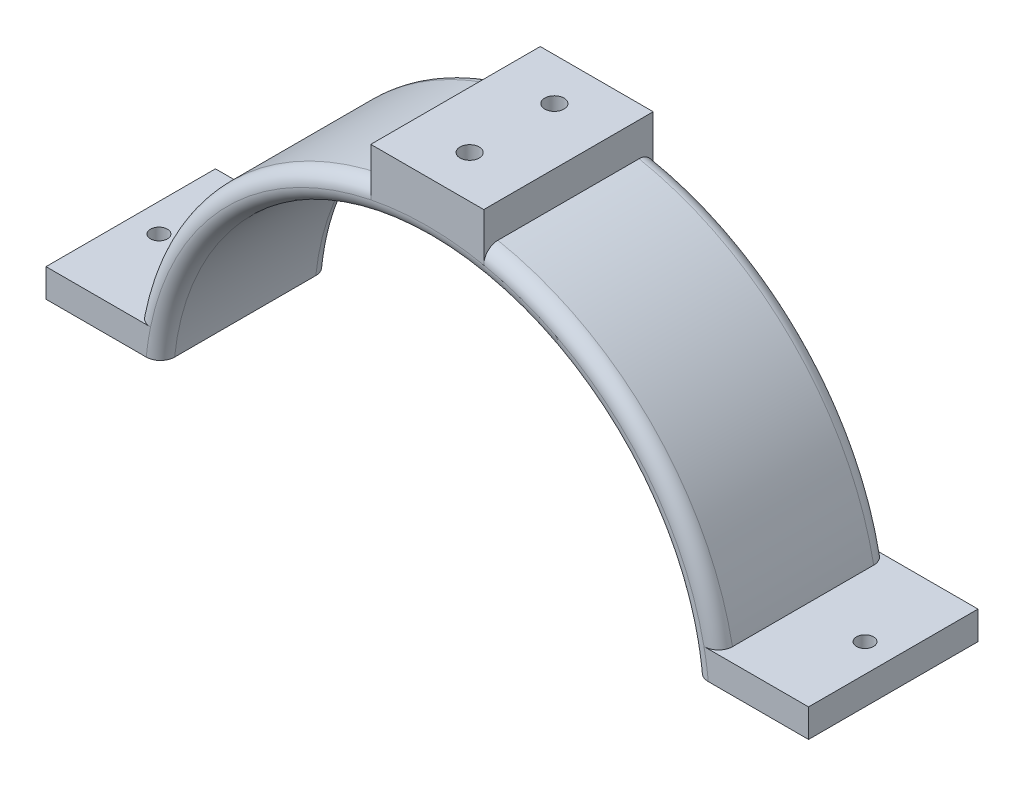
SolidWorks part; units mm, degrees
ref_plane "Front Plane" through (0, 0, 0) normal (0, 0, 1) x (1, 0, 0)
ref_plane "Top Plane" through (0, 0, 0) normal (0, 1, 0) x (1, 0, 0)
ref_plane "Right Plane" through (0, 0, 0) normal (1, 0, 0) x (0, 0, -1)
sketch "Sketch1" plane through (0, 0, 0) normal (0, 0, 1) x (1, 0, 0)
  line L0 (47.2361, 5) -> (67.5, 5)
  line L3 (-67.5, 5) -> (-47.2361, 5)
  line L6 (-10, 57.5) -> (10, 57.5)
  line L9 (-51.5388, 10) -> (-67.5, 10)
  line L10 (-67.5, 5) -> (-67.5, 10)
  line L13 (51.5388, 10) -> (67.5, 10)
  line L14 (67.5, 5) -> (67.5, 10)
  line L15 (-10, 57.5) -> (-10, 51.5388)
  line L17 (10, 57.5) -> (10, 51.5388)
  arc A2 (47.2361, 5) -> (-47.2361, 5) centre (0, 0) ccw
  arc A3 (51.5388, 10) -> (10, 51.5388) centre (0, 0) ccw
  arc A4 (-10, 51.5388) -> (-51.5388, 10) centre (0, 0) ccw
  dimension "D1" = 5
  dimension "D2" = 94.4722
  dimension "D8" = 5.9612
  dimension "D3" = 5
  dimension "D4" = 15.9612
  dimension "D5" = 15.9612
  dimension "D6" = 20.2639
  dimension "D7" = 20.2639
  dimension "D9" = 20
extrude "Boss-Extrude1" add sketch "Sketch1" along normal blind 30
fillet "Fillet1" radius 2.5 6 edges at (37.1231, 37.1231, 0) (0, 47.5, 0) (-37.1231, 37.1231, 0) (-37.1231, 37.1231, 30) (37.1231, 37.1231, 30) (0, 47.5, 30)
sketch "Sketch6" plane through (0, 5, 0) normal (0, -1, 0) x (1, 0, 0)
  line L0 (-47.2361, 2.5) -> (47.2361, 2.5) construction
  circle A0 centre (0, 22.5) radius 3.75
  circle A1 centre (0, 7.5) radius 3.75
  dimension "D1" = 7.5
  dimension "D2" = 7.5
  dimension "D3" = 15
  dimension "D4" = 5
extrude "Cut-Extrude1" cut sketch "Sketch6" against normal blind 47.5
hole_wizard "CSK for M3 Flat Head Machine Screw1" positions "Sketch7" profile "Sketch8" countersink size "M3" standard "ANSI Metric" end condition through all
sketch "Sketch7" plane through (0, 52.5, 0) normal (0, -1, 0) x (-1, 0, 0)
  point P0 (0, -22.5)
  point P3 (0, -7.5)
sketch "Sketch8" plane through (0, 52.5, 22.5) normal (1, 0, 0) x (0, 0, -1)
  line L0 (0, 0) -> (0, 5)
  line L1 (0, 5) -> (1.7, 5)
  line L2 (1.7, 5) -> (1.7, 1.45)
  line L3 (1.7, 1.45) -> (3.15, 0)
  line L5 (3.15, 0) -> (0, 0)
  line L6 (-1.7, 1.45) -> (-3.15, 0) construction
  line L11 (0, -6.35) -> (0, 107.95) construction
  dimension "Thru Hole Dia." = 3.4
  dimension "Thru Hole Depth" = 5
  dimension "Near C'Sink Dia." = 6.3
  dimension "Near C'Sink Angle" = 90
hole_wizard "Ø3.0mm Dowel Hole1" positions "Sketch9" profile "Sketch10" hole size "Ø3.0" standard "ANSI Metric" end condition through all
sketch "Sketch9" plane through (0, 10, 0) normal (0, 1, 0) x (1, 0, 0)
  line L1 (-67.5, -30) -> (-67.5, 0) construction
  line L2 (-48.9898, -30) -> (-67.5, -30) construction
  line L3 (67.5, -30) -> (48.9898, -30) construction
  line L4 (67.5, -30) -> (67.5, 0) construction
  point P0 (-62.5, -15)
  point P2 (62.5, -15)
  dimension "D1" = 5
  dimension "D2" = 15
  dimension "D3" = 15
  dimension "D4" = 5
sketch "Sketch10" plane through (-62.5, 10, 15) normal (1, 0, 0) x (0, 0, 1)
  line L0 (0, 0) -> (0, 5)
  line L1 (0, 5) -> (1.5, 5)
  line L2 (1.5, 5) -> (1.5, 0)
  line L5 (1.5, 0) -> (0, 0)
  line L11 (0, -6.35) -> (0, 107.95) construction
  dimension "Thru Hole Dia." = 3
  dimension "Thru Hole Depth" = 5
